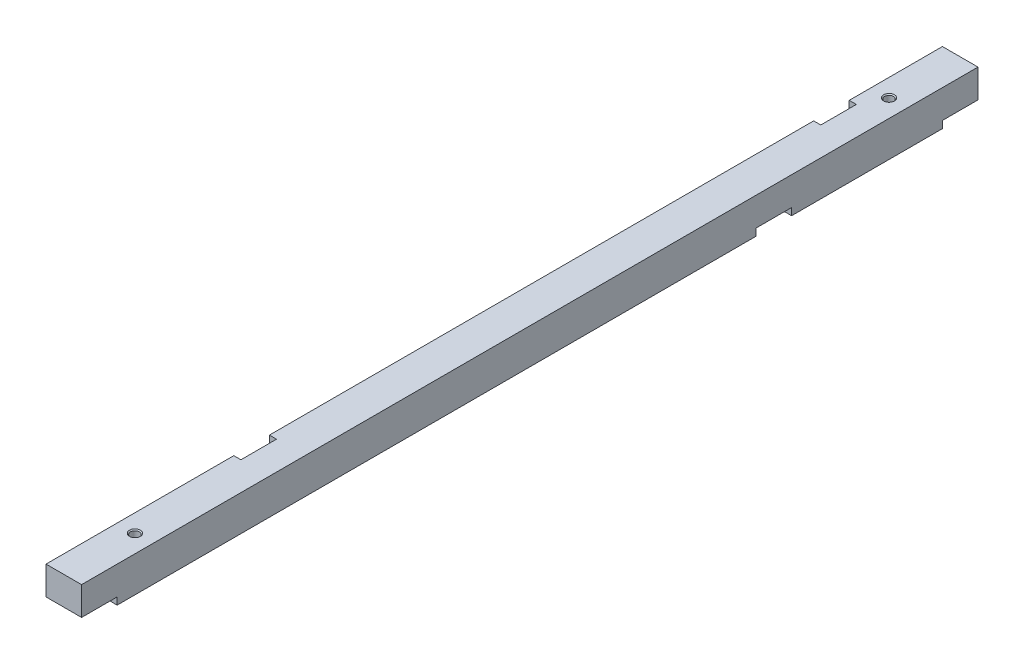
SolidWorks part; units mm, degrees
ref_plane "Plan de face" through (0, 0, 0) normal (0, 0, 1) x (1, 0, 0)
ref_plane "Plan de dessus" through (0, 0, 0) normal (0, 1, 0) x (1, 0, 0)
ref_plane "Plan de droite" through (0, 0, 0) normal (1, 0, 0) x (0, 0, -1)
sketch "Esquisse1" plane through (0, 0, 0) normal (0, 0, 1) x (1, 0, 0)
  line L0 (-5, 5) -> (5, -5) construction
  line L1 (-5, 5) -> (5, 5)
  line L2 (-5, 5) -> (-5, -5)
  line L3 (-5, -5) -> (5, -5)
  line L4 (5, 5) -> (5, -5)
  dimension "D1" = 10
extrude "Boss.-Extru.1" add sketch "Esquisse1" along normal blind 252
sketch "Esquisse2" plane through (-5, 0, 0) normal (-1, 0, 0) x (0, 0, 1)
  line L0 (0, -3) -> (0, -303) construction
  line L1 (0, -5) -> (10, -5)
  line L2 (0, -5) -> (0, -3)
  line L3 (0, -3) -> (10, -3)
  line L4 (10, -5) -> (10, -3)
  line L5 (10, -3) -> (10, -170) construction
  line L6 (52.4, -3) -> (52.4, -170) construction
  line L7 (52.4, -5) -> (62.4, -5)
  line L8 (52.4, -5) -> (52.4, -3)
  line L9 (52.4, -3) -> (62.4, -3)
  line L10 (62.4, -5) -> (62.4, -3)
  line L11 (62.4, -3) -> (62.4, -170) construction
  line L12 (242, -3) -> (242, -170) construction
  line L13 (242, -5) -> (252, -5)
  line L14 (242, -5) -> (242, -3)
  line L15 (242, -3) -> (252, -3)
  line L16 (252, -5) -> (252, -3)
  line L17 (252, -3) -> (252, -297.8) construction
  line L18 (252, -5) -> (0, -5) construction
  dimension "D1" = 2
extrude "Enlèv. mat.-Extru.1" cut sketch "Esquisse2" against normal through all
sketch "Esquisse3" plane through (0, -5, 0) normal (0, -1, 0) x (1, 0, 0)
  line L4 (3, 36.2) -> (3, 26.2)
  line L5 (234, 36.2) -> (3, 36.2)
  line L6 (234, 26.2) -> (234, 36.2)
  line L7 (3, 26.2) -> (234, 26.2)
  line L8 (3, 36.2) -> (3, 26.2)
  line L9 (234, 36.2) -> (3, 36.2)
  line L10 (234, 26.2) -> (234, 36.2)
  line L11 (3, 26.2) -> (234, 26.2)
  dimension "D1" = 0
extrude "Enlèv. mat.-Extru.2" [suppressed] cut sketch "Esquisse3" against normal through all
sketch "Esquisse4" plane through (0, 5, 0) normal (0, 1, 0) x (1, 0, 0)
  line L4 (3, -189.2) -> (3, -199.2)
  line L5 (3, -199.2) -> (234, -199.2)
  line L6 (234, -199.2) -> (234, -189.2)
  line L7 (234, -189.2) -> (3, -189.2)
  line L8 (3, -189.2) -> (3, -199.2)
  line L9 (3, -199.2) -> (234, -199.2)
  line L10 (234, -199.2) -> (234, -189.2)
  line L11 (234, -189.2) -> (3, -189.2)
  dimension "D1" = 0
extrude "Enlèv. mat.-Extru.3" [suppressed] cut sketch "Esquisse4" against normal through all
sketch "Esquisse5" plane through (0, 5, 0) normal (0, 1, 0) x (1, 0, 0)
  line L0 (3, -199.2) -> (234, -199.2) construction
  line L1 (-5, -199.2) -> (-3, -199.2)
  line L2 (-5, -199.2) -> (-5, -189.2)
  line L3 (-5, -189.2) -> (-3, -189.2)
  line L4 (-3, -199.2) -> (-3, -189.2)
  line L5 (3, -189.2) -> (234, -189.2) construction
  line L6 (3, -36.2) -> (234, -36.2) construction
  line L7 (-5, -36.2) -> (-3, -36.2)
  line L8 (-5, -36.2) -> (-5, -26.2)
  line L9 (-5, -26.2) -> (-3, -26.2)
  line L10 (-3, -36.2) -> (-3, -26.2)
  line L11 (3, -26.2) -> (234, -26.2) construction
  line L12 (-5, -252) -> (-5, 0) construction
  dimension "D1" = 2
extrude "Enlèv. mat.-Extru.4" cut sketch "Esquisse5" against normal through all
hole_wizard "Trou taraudé M3x0.51" positions "Esquisse7" profile "Esquisse6" tap size "M3x0.5" standard "Ansi Metric" end condition through all
sketch "Esquisse7" plane through (0, 5, 0) normal (0, 1, 0) x (1, 0, 0)
  point P0 (0, -20)
  point P3 (0, -232)
sketch "Esquisse6" plane through (0, 5, 20) normal (1, 0, 0) x (0, 0, 1)
  line L0 (0, 0) -> (0, 10)
  line L1 (0, 10) -> (1.25, 10)
  line L2 (1.25, 10) -> (1.25, 0.275)
  line L3 (1.25, 0.275) -> (1.525, 0)
  line L5 (1.525, 0) -> (0, 0)
  line L6 (-1.25, 0.275) -> (-1.525, 0) construction
  line L11 (0, -6.35) -> (0, 107.95) construction
  dimension "Diamètre du trou pour taraudage jusqu'au prochain" = 2.5
  dimension "Profondeur du trou pour taraudage jusqu'au prochain" = 10
  dimension "Diamètre du fraisage entrant" = 3.05
  dimension "Angle du fraisage entrant" = 90
cosmetic thread "Filetage de perçage1" parameters "D2"=3
cosmetic thread "Filetage de perçage2" parameters "D2"=3
